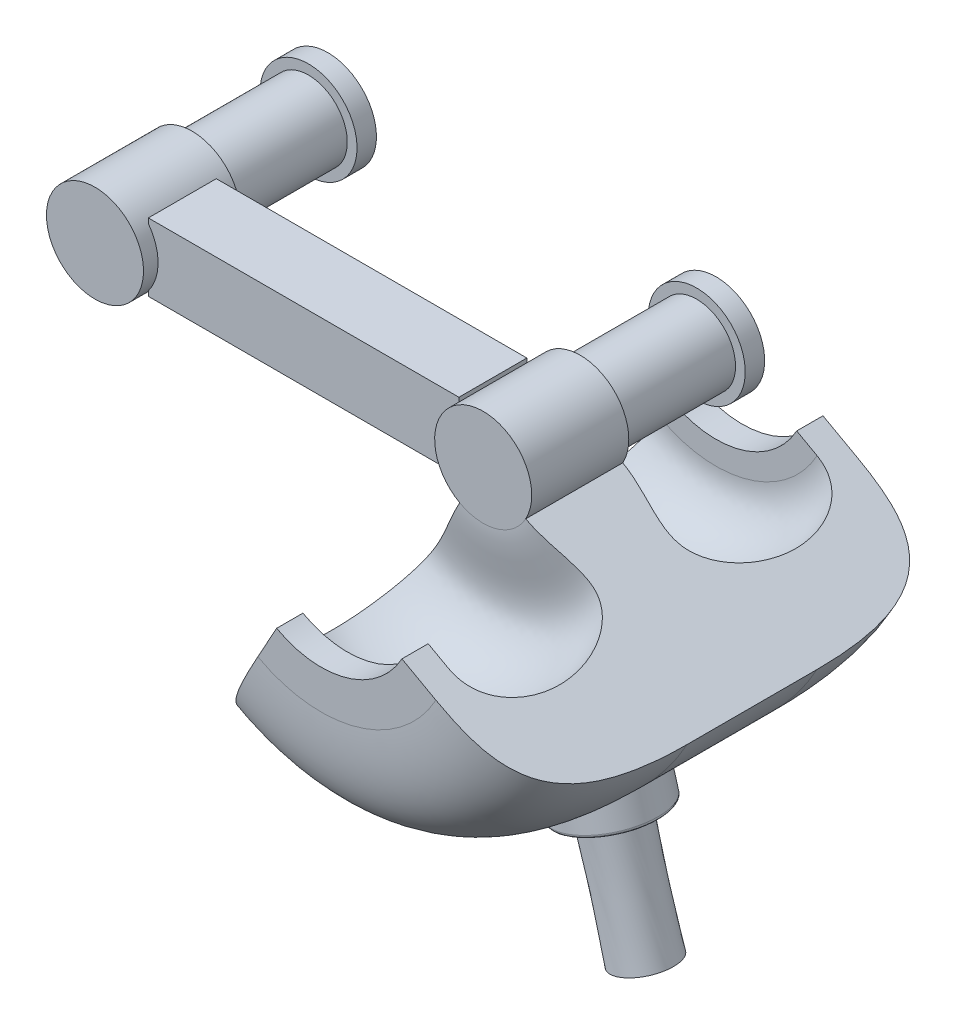
SolidWorks part; units mm, degrees
ref_plane "Front Plane" through (0, 0, 0) normal (0, 0, 1) x (1, 0, 0)
ref_plane "Top Plane" through (0, 0, 0) normal (0, 1, 0) x (1, 0, 0)
ref_plane "Right Plane" through (0, 0, 0) normal (1, 0, 0) x (0, 0, -1)
sketch "Sketch1" plane through (0, 0, 0) normal (0, 0, 1) x (1, 0, 0)
  line L0 (100, 0) -> (-100, 0)
  line L1 (-100, 0) -> (-84.615, -53.2945) construction
  line L2 (-84.615, -53.2945) -> (100, 0) construction
  line L3 (-84.615, -53.2945) -> (-100, 0) construction
  line L4 (-100, 0) -> (-148.4737, 167.9155) construction
  line L5 (-100, 0) -> (-115.2545, 52.8422)
  line L6 (-100, 0) -> (84.615, 53.2945) construction
  line L7 (84.615, 53.2945) -> (100, 0) construction
  line L8 (84.615, 53.2945) -> (100, 0) construction
  line L9 (100, 0) -> (139.1778, -135.7138) construction
  line L10 (100, 0) -> (115.2545, -52.8422)
  circle A0 centre (-100, 0) radius 25
  circle A1 centre (100, 0) radius 25
  point P4 (0, 0)
  dimension "D2" = 16.102
  dimension "D1" = 200
  dimension "D3" = 55
  dimension "D4" = 16.102
  dimension "D5" = 55
sketch "Sketch2" plane through (0, 0, 0) normal (0, 1, 0) x (1, 0, 0)
  line L0 (-100, -30.0778) -> (-100, 0) construction
  line L1 (-120, 0) -> (-111.4048, -6.7332)
  line L2 (-120, 0) -> (-100, 0)
  line L3 (-105, -30.0778) -> (-105, -15.0778)
  line L4 (-100, 0) -> (-100, -30.0778)
  line L5 (-100, -30.0778) -> (-105, -30.0778)
  line L6 (-125, 0) -> (-75, 0) construction
  line L9 (-125, -5) -> (-125, -7.9927) construction
  line L10 (-125, -5) -> (-125, -15.0778)
  line L11 (-115, -15.0778) -> (-125, -15.0778)
  line L12 (-125, -5) -> (-125, 0)
  line L13 (-125, 0) -> (-120, 0)
  line L14 (-113.6173, -5) -> (-113.6173, -15.0778)
  line L15 (-113.6173, -15.0778) -> (-115, -15.0778)
  line L16 (-113.6173, -15.0778) -> (-105, -15.0778)
  spline S0 degree 3 poles (-111.4048, -6.7332) (-109.6654, -8.0958) (-107.132, -10.6266) (-105, -13.4894) (-105, -15.0778) knots 0 0 0 0 0.616179 1 1 1 1
  dimension "D1" = 5
  dimension "D2" = 20
  dimension "D3" = 10.9185
  dimension "D4" = 15
  dimension "D5" = 5
  dimension "D6" = 5
  dimension "D7" = 5
  dimension "D8" = 10
  dimension "D9" = 15
  dimension "D10" = 15.0778
sketch "Sketch3" plane through (0, 0, 0) normal (0, 1, 0) x (1, 0, 0)
  line L5 (-125, -7.5389) -> (-80.1507, -7.5389) construction
  line L8 (-120, 0) -> (-100, 0) construction
  line L9 (-125, -32.5389) -> (-125, 17.4611)
  line L10 (-100, 0) -> (-100, 17.4611)
  line L11 (-100, 17.4611) -> (-125, 17.4611)
  line L12 (-100, 0) -> (-100, -15.0778)
  line L13 (-100, 0) -> (-100, -30.0778) construction
  line L14 (-100, -15.0778) -> (-100, -32.5389)
  line L15 (-100, -32.5389) -> (-125, -32.5389)
  point P10 (-100, -7.5389)
  dimension "D1" = 7.5389
  dimension "D2" = 25
revolve "Revolve2" add sketch "Sketch3" angle 360 about L4
sketch "Sketch4" plane through (0, 0, 0) normal (0, 0, 1) x (1, 0, 0)
  circle A0 centre (100, 0) radius 25
ref_plane "Plane1" through (80, 0, 0) normal (1, 0, 0) x (0, 0, -1)
ref_plane "Plane2" through (-80, 0, 0) normal (1, 0, 0) x (0, 0, -1)
sketch "Sketch5" plane through (80, 0, 0) normal (1, 0, 0) x (0, 0, -1)
  line L11 (9.9611, -17.5) -> (-25.0389, -17.5)
  line L12 (9.9611, -17.5) -> (9.9611, 17.5)
  line L13 (9.9611, 17.5) -> (-25.0389, 17.5)
  line L14 (-25.0389, -17.5) -> (-25.0389, 17.5)
  point P12 (-7.5389, 0)
  dimension "D1" = 35
  dimension "D2" = 35
sketch "Sketch6" plane through (-80, 0, 0) normal (1, 0, 0) x (0, 0, -1)
  line L12 (9.9611, -17.5) -> (-25.0389, -17.5)
  line L13 (9.9611, -17.5) -> (9.9611, 17.5)
  line L14 (9.9611, 17.5) -> (-25.0389, 17.5)
  line L15 (-25.0389, -17.5) -> (-25.0389, 17.5)
  point P6 (-7.5389, 0)
  dimension "D1" = 35
  dimension "D2" = 35
sketch "Sketch7" plane through (0, 0, 0) normal (1, 0, 0) x (0, 0, -1)
  line L0 (-7.5389, 45) -> (-7.5389, -15)
  point P3 (-7.5389, 15)
ref_plane "Plane3" through (0, 0, 7.5389) normal (0, 0, 1) x (1, 0, 0)
loft "Loft2" add profiles "Sketch6", "Sketch5" connector at (-80, -17.5, -9.9611) connector at (80, -17.5, -9.9611)
sketch "Sketch10" plane through (0, 0, 7.5389) normal (0, 0, 1) x (1, 0, 0)
  circle A0 centre (100, 0) radius 25
extrude "Boss-Extrude2" add sketch "Sketch10" along normal mid plane 50
sketch "Sketch11" plane through (0, 0, 7.5389) normal (0, 0, 1) x (1, 0, 0)
  line L0 (100, 0) -> (115.2545, -52.8422) construction
ref_plane "Plane4" through (7.6925, -26.6473, 0) normal (0.2774, -0.9608, 0) x (-0.9608, -0.2774, 0)
ref_plane "Plane5" through (92.3075, 26.6473, 0) normal (0.9608, 0.2774, 0) x (0, 0, -1)
sketch "Sketch12" plane through (92.3075, 26.6473, 0) normal (0.9608, 0.2774, 0) x (0, 0, -1)
  line L0 (-32.5389, -75.009) -> (17.4611, -75.009) construction
  line L1 (-32.5389, -2.7354) -> (-32.5389, -52.7354) construction
  line L2 (17.4611, -52.7354) -> (17.4611, -2.7354) construction
  line L3 (-7.5389, -84.4009) -> (-7.5389, -65.617)
  line L4 (-22.5389, -65.617) -> (-47.5389, -65.617)
  line L5 (-47.5389, -65.617) -> (-47.5389, -78.1293)
  line L6 (-7.5389, -65.617) -> (-7.5389, -132.7956) construction
  line L7 (-22.5389, -65.617) -> (-22.5389, -52.7354)
  line L8 (-32.5389, -52.7354) -> (17.4611, -52.7354) construction
  line L9 (-127.5389, -120.3474) -> (-132.5389, -120.3474)
  line L10 (-132.5389, -120.3474) -> (-132.5389, -150.3474)
  line L11 (-132.5389, -150.3474) -> (-112.5389, -150.3474)
  line L12 (-112.5389, -150.3474) -> (-112.5389, -128.4544)
  line L13 (-47.5389, -108.1293) -> (32.4611, -108.1293)
  line L14 (-90.9173, -108.1293) -> (-47.5389, -108.1293)
  line L15 (117.4611, -120.3474) -> (117.4611, -150.3474)
  line L16 (117.4611, -150.3474) -> (97.4611, -150.3474)
  line L17 (97.4611, -150.3474) -> (97.4611, -128.4544)
  line L18 (75.8395, -108.1293) -> (32.4611, -108.1293)
  line L19 (32.4611, -65.617) -> (32.4611, -78.1293)
  line L20 (7.4611, -65.617) -> (32.4611, -65.617)
  line L21 (7.4611, -65.617) -> (7.4611, -52.7354)
  line L22 (112.4611, -120.3474) -> (117.4611, -120.3474)
  line L23 (-112.5389, -139.4009) -> (-7.5389, -139.4009) construction
  line L24 (-32.5389, -27.7354) -> (-61.8307, -27.7354) construction
  spline S0 degree 3 poles (-47.5389, -78.1293) (-56.791, -78.1293) (-92.4711, -91.2818) (-119.9145, -99.872) (-127.5389, -120.3474) knots 0 0 0 0 0.409199 1 1 1 1
  spline S1 degree 2 poles (-112.5389, -128.4544) (-109.5542, -110.7568) (-90.9173, -108.1293) knots 0 0 0 1 1 1
  spline S2 degree 2 poles (97.4611, -128.4544) (94.4764, -110.7568) (75.8395, -108.1293) knots 0 0 0 1 1 1
  spline S3 degree 3 poles (32.4611, -78.1293) (41.7132, -78.1293) (77.3933, -91.2818) (104.8367, -99.872) (112.4611, -120.3474) knots 0 0 0 0 0.409199 1 1 1 1
  point P9 (-7.5389, -75.009)
  point P30 (-7.5389, -108.1293)
  dimension "D1" = 120
  dimension "D2" = 40
  dimension "D3" = 15
  dimension "D4" = 15
  dimension "D5" = 20
  dimension "D6" = 30
  dimension "D7" = 15
  dimension "D8" = 20
  dimension "D9" = 30
  dimension "D10" = 55
  dimension "D11" = 111.6655
sketch "Sketch13" plane through (92.3075, 26.6473, 0) normal (0.9608, 0.2774, 0) x (0, 0, -1)
  line L0 (-7.5389, -52.7354) -> (-7.5389, -82.7354) construction
  line L1 (-32.5389, -52.7354) -> (17.4611, -52.7354) construction
  line L2 (-32.5389, -27.7354) -> (-7.5389, -27.7354) construction
  line L3 (-32.5389, -2.7354) -> (-32.5389, -52.7354) construction
  line L4 (-7.5389, -27.7354) -> (-7.5389, -52.7354) construction
  line L5 (-7.5389, -82.7354) -> (-107.5389, -82.7354) construction
  line L6 (-41.0034, -157.4201) -> (25.9256, -157.4201)
  line L8 (-102.4645, -87.2354) -> (-102.4645, -75.2354)
  line L9 (-102.4645, -75.2354) -> (-115.9963, -75.2354)
  line L10 (-115.9963, -95.2354) -> (-115.9963, -75.2354)
  line L11 (-102.4645, -87.2354) -> (-115.9963, -75.2354) construction
  line L12 (-102.4645, -75.2354) -> (-115.9963, -95.2354) construction
  line L13 (-32.5389, -52.7354) -> (17.4611, -52.7354)
  line L14 (100.9185, -95.2354) -> (100.9185, -75.2354)
  line L15 (87.3867, -75.2354) -> (100.9185, -75.2354)
  line L16 (87.3867, -87.2354) -> (87.3867, -75.2354)
  line L17 (-7.5389, -27.7354) -> (-7.5389, 682.2646) construction
  line L18 (-7.5389, 682.2646) -> (-163.5255, 682.2646) construction
  spline S0 degree 3 poles (-32.5389, -52.7354) (-32.5389, -66.8651) (-17.6807, -96.9933) (-69.7739, -123.2553) (-102.4645, -103.261) (-102.4645, -87.2354) knots 0 0 0 0 0.304905 0.682398 1 1 1 1
  spline S1 degree 3 poles (-115.9963, -95.2354) (-115.9963, -103.8192) (-114.0214, -138.7604) (-92.6443, -157.4201) (-41.0034, -157.4201) knots 0 0 0 0 0.21752 1 1 1 1
  spline S2 degree 3 poles (100.9185, -95.2354) (100.9185, -103.8192) (98.9436, -138.7604) (77.5665, -157.4201) (25.9256, -157.4201) knots 0 0 0 0 0.21752 1 1 1 1
  spline S3 degree 3 poles (17.4611, -52.7354) (17.4611, -66.8651) (2.6029, -96.9933) (54.6961, -123.2553) (87.3867, -103.261) (87.3867, -87.2354) knots 0 0 0 0 0.304905 0.682398 1 1 1 1
  point P20 (-7.5389, -157.4201)
  dimension "D1" = 55
  dimension "D2" = 100
  dimension "D3" = 20
  dimension "D4" = 710
sketch "Sketch14" plane through (92.3075, 26.6473, 0) normal (0.9608, 0.2774, 0) x (0, 0, -1)
  line L0 (-7.5389, -27.7354) -> (-7.5389, 682.2646) construction
  dimension "D1" = 710
sketch "Sketch15" plane through (92.3075, 26.6473, 0) normal (0.9608, 0.2774, 0) x (0, 0, -1)
  line L0 (201.0989, 682.2646) -> (-216.1768, 682.2646)
  point P4 (-7.5389, 682.2646)
ref_plane "Plane6" through (82.6998, 23.8737, 0) normal (0.9608, 0.2774, 0) x (0, 0, -1)
revolve "Revolve3" add sketch "Sketch13" angle 90 mid plane about L2
sketch "Sketch16" plane through (0, 0, 7.5389) normal (0, 0, 1) x (1, 0, 0)
  line L0 (87.9188, -21.8871) -> (101.0838, -67.4913)
  line L3 (100, 0) -> (115.2545, -52.8422) construction
  line L4 (87.9188, -21.8871) -> (67.3808, -59.0952)
  arc A0 (67.3808, -59.0952) -> (159.0952, -32.6192) centre (100, 0) ccw construction
  arc A4 (67.3808, -59.0952) -> (101.0838, -67.4913) centre (100, 0) ccw
sketch "Sketch18" plane through (0, 0, 7.5389) normal (0, 0, 1) x (1, 0, 0)
  line L0 (84.615, 53.2945) -> (139.1778, -135.7138) construction
  line L1 (139.1778, -135.7138) -> (158.5925, -202.9675) construction
  dimension "D1" = 70
ref_plane "Plane7" through (35.4279, -122.724, 0) normal (0.2774, -0.9608, 0) x (-0.9608, -0.2774, 0)
sketch "Sketch19" plane through (35.4279, -122.724, 0) normal (0.2774, -0.9608, 0) x (-0.9608, -0.2774, 0)
  circle A0 centre (-96.0768, -7.5389) radius 25
  point P3 (-96.0768, -7.5389)
  point P8 (-96.0768, -81.7676)
extrude "Boss-Extrude3" add sketch "Sketch19" along normal blind 50
ref_plane "Plane8" through (66.285, -229.6148, 0) normal (0.2774, -0.9608, 0) x (-0.9608, -0.2774, 0)
sketch "Sketch20" plane through (66.285, -229.6148, 0) normal (0.2774, -0.9608, 0) x (-0.9608, -0.2774, 0)
  line L0 (-187.7777, -7.5389) -> (-89.9025, -7.5389) construction
  line L1 (-187.7777, -41.0034) -> (-187.7777, 25.9256) construction
  line L2 (-96.0768, 100.9185) -> (-96.0768, -7.5389) construction
  line L3 (-48.3471, 100.9185) -> (-143.8065, 100.9185) construction
  circle A0 centre (-96.0768, -7.5389) radius 15
sketch "Sketch21" plane through (92.3075, 26.6473, 0) normal (0.9608, 0.2774, 0) x (0, 0, -1)
  line L0 (-22.5389, -177.7354) -> (-22.5389, -238.9909)
  line L1 (-7.5389, -168.9909) -> (-7.5389, -238.9909) construction
  line L10 (-22.5389, -238.9909) -> (7.4611, -238.9909) construction
  line L11 (-7.5389, -238.9909) -> (-7.5389, -168.9909) construction
  line L12 (-7.5389, 27.7354) -> (-7.5389, -168.9909) construction
  line L13 (7.4611, -177.7354) -> (7.4611, -238.9909)
  dimension "D1" = 15
sketch "Sketch22" plane through (49.2956, -170.7624, 0) normal (0.2774, -0.9608, 0) x (0.9608, 0.2774, 0)
  circle A0 centre (96.0768, 7.5389) radius 15
loft "Loft4" add profiles "Sketch22", "Sketch20" connector at (127.883, -148.0759, 12.1293) connector at (148.9404, -205.7539, 18.6777)
fillet "Fillet6" radius 1.5 2 edges at (156.0146, -139.9549, 7.5389) (165.6223, -137.1813, 7.5389)
sketch "Sketch25" plane through (0, 0, -17.4611) normal (0, 0, -1) x (-1, 0, 0)
  circle A0 centre (100, 0) radius 20
extrude "Boss-Extrude4" add sketch "Sketch25" along normal blind 60
sketch "Sketch26" plane through (0, 0, -77.4611) normal (0, 0, -1) x (-1, 0, 0)
  circle A0 centre (100, 0) radius 25
extrude "Boss-Extrude5" add sketch "Sketch26" along normal blind 10
sketch "Sketch27" plane through (0, 0, -17.4611) normal (0, 0, -1) x (-1, 0, 0)
  circle A0 centre (-100, 0) radius 20
extrude "Boss-Extrude6" add sketch "Sketch27" along normal blind 60
sketch "Sketch28" plane through (0, 0, -77.4611) normal (0, 0, -1) x (-1, 0, 0)
  circle A0 centre (-100, 0) radius 25
extrude "Boss-Extrude7" add sketch "Sketch28" along normal blind 10
